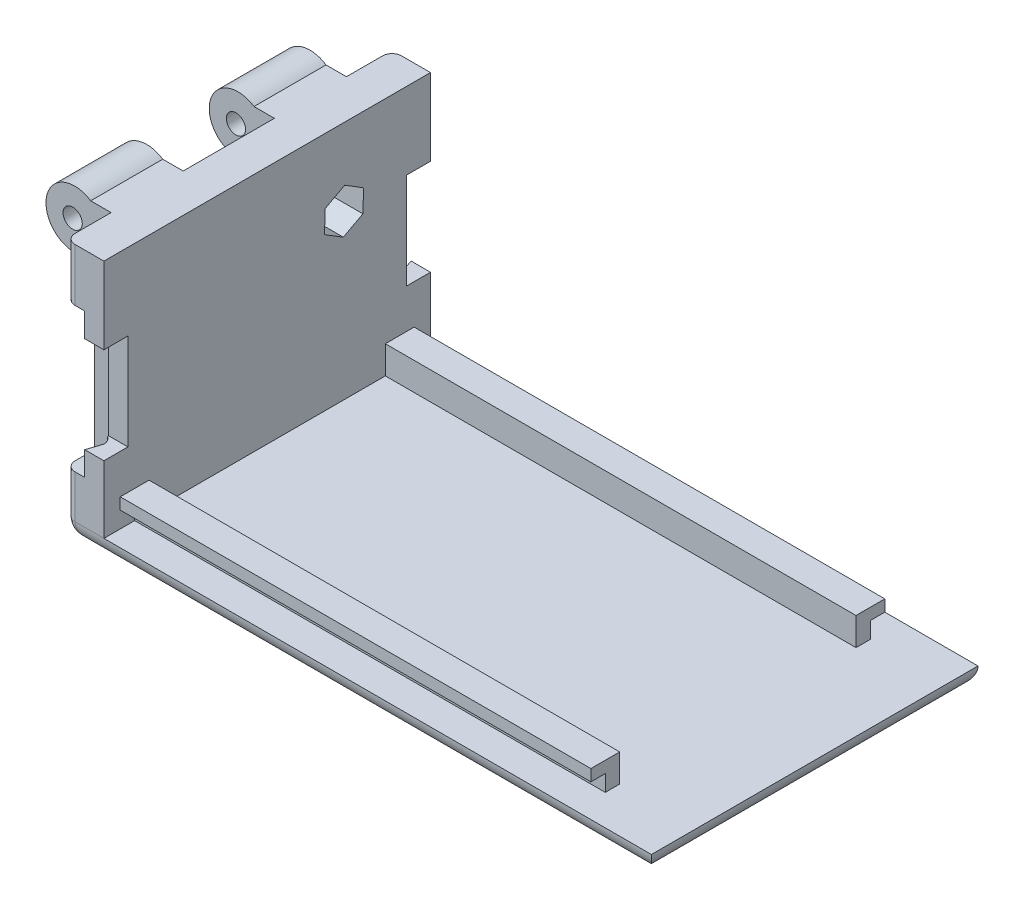
SolidWorks part; units mm, degrees
ref_plane "Front Plane" through (0, 0, 0) normal (0, 0, 1) x (1, 0, 0)
ref_plane "Top Plane" through (0, 0, 0) normal (0, 1, 0) x (1, 0, 0)
ref_plane "Right Plane" through (0, 0, 0) normal (1, 0, 0) x (0, 0, -1)
sketch "Sketch1" plane through (0, 0, 0) normal (0, 1, 0) x (1, 0, 0)
  line L1 (0, 0) -> (61, 0)
  line L2 (0, 0) -> (0, 34)
  line L3 (0, 34) -> (61, 34)
  line L4 (61, 0) -> (61, 34)
  line L5 (0, 0) -> (61, 34) construction
  line L6 (0, 34) -> (61, 0) construction
  point P4 (30.5, 17)
  dimension "D1" = 34
  dimension "D2" = 61
extrude "Boss-Extrude1" add sketch "Sketch1" along normal blind 2
sketch "Sketch2" plane through (0, 2, 0) normal (0, 1, 0) x (1, 0, 0)
  line L0 (61, 34) -> (0, 34) construction
  line L1 (0, 0) -> (4, 0)
  line L2 (0, 0) -> (0, 34)
  line L3 (0, 34) -> (4, 34)
  line L4 (4, 0) -> (4, 34)
  line L5 (0, 0) -> (4, 34) construction
  line L6 (0, 34) -> (4, 0) construction
  point P4 (2, 17)
  dimension "D1" = 4
extrude "Boss-Extrude2" add sketch "Sketch2" along normal blind 25 contours L4 L3 L2 L1
sketch "Sketch3" plane through (4, 0, 0) normal (1, 0, 0) x (0, 0, -1)
  line L0 (0, 2) -> (34, 2) construction
  line L1 (4.7, 2) -> (3.2, 2)
  line L2 (4.7, 2) -> (4.7, 4.9)
  line L3 (4.7, 4.9) -> (3.2, 4.9)
  line L4 (3.2, 2) -> (3.2, 4.9)
  line L5 (4.7, 2) -> (3.2, 4.9) construction
  line L6 (4.7, 4.9) -> (3.2, 2) construction
  line L7 (0, 27) -> (0, 2) construction
  line L8 (3.2, 4.9) -> (1.7, 4.9)
  line L9 (3.2, 4.9) -> (3.2, 3.7)
  line L10 (3.2, 3.7) -> (1.7, 3.7)
  line L11 (1.7, 4.9) -> (1.7, 3.7)
  line L12 (3.2, 4.9) -> (1.7, 3.7) construction
  line L13 (3.2, 3.7) -> (1.7, 4.9) construction
  line L14 (17, 2) -> (17, 9.9529) construction
  line L15 (30.8, 3.7) -> (32.3, 3.7)
  line L16 (32.3, 4.9) -> (32.3, 3.7)
  line L17 (30.8, 4.9) -> (32.3, 4.9)
  line L18 (30.8, 4.9) -> (30.8, 3.7)
  line L19 (29.3, 4.9) -> (30.8, 4.9)
  line L20 (30.8, 2) -> (30.8, 4.9)
  line L21 (29.3, 2) -> (30.8, 2)
  line L22 (29.3, 2) -> (29.3, 4.9)
  point P4 (3.95, 3.45)
  point P10 (2.45, 4.3)
  dimension "D1" = 1.2
  dimension "D2" = 2.9
  dimension "D3" = 1.5
  dimension "D4" = 3.2
  dimension "D5" = 1.5
extrude "Boss-Extrude3" add sketch "Sketch3" along normal blind 49 contours L17 L18 L15 L16 | L4 L1 L2 L3 | L8 L11 L10 L9 | L20 L21 L22 L19 region at (4, 4.3, -31.55)
sketch "Sketch4" plane through (0, 0, 0) normal (0, 0, 1) x (1, 0, 0)
  line L0 (0, 27) -> (0, 0) construction
  line L1 (4, 27) -> (0, 27)
  line L2 (4, 27) -> (4, 22)
  line L3 (4, 22) -> (0, 22)
  line L5 (4, 27) -> (-5, 22) construction
  line L6 (4, 22) -> (-3.9994, 26.8988) construction
  line L8 (0, 22) -> (-2.1254, 22)
  line L9 (0, 27) -> (-2.1254, 27)
  line L10 (0, 22) -> (0, 27)
  circle A1 centre (-3.7837, 24.5) radius 3
  point P4 (-0.281, 24.6217)
  line M12 (0, 27) -> (0, 0)
  dimension "D3" = 6
  dimension "D1" = 8
  dimension "D2" = 5
extrude "Boss-Extrude4" add sketch "Sketch4" against normal blind 30 contours M12 | A1 region at (-0.6518, 24.5, 0)
sketch "Sketch5" plane through (0, 0, 0) normal (0, -1, 0) x (1, 0, 0)
  line L0 (0, -34) -> (0, 0) construction
  line L1 (0, 0) -> (-8, 0)
  line L2 (0, 0) -> (0, -4.75)
  line L3 (0, -4.75) -> (-8, -4.75)
  line L4 (-8, 0) -> (-8, -4.75)
  line L5 (0, 0) -> (-8, -4.75) construction
  line L6 (0, -4.75) -> (-8, 0) construction
  line L7 (61, -34) -> (0, -34) construction
  line L8 (0, -29.25) -> (-8, -29.25)
  line L9 (0, -29.25) -> (0, -34)
  line L10 (0, -34) -> (-8, -34)
  line L11 (-8, -29.25) -> (-8, -34)
  line L12 (0, -29.25) -> (-8, -34) construction
  line L13 (0, -34) -> (-8, -29.25) construction
  line L14 (0, 0) -> (61, 0) construction
  line L16 (0, -12.25) -> (-8, -12.25)
  line L17 (0, -12.25) -> (0, -21.75)
  line L18 (0, -21.75) -> (-8, -21.75)
  line L19 (-8, -12.25) -> (-8, -21.75)
  line L20 (0, -12.25) -> (-8, -21.75) construction
  line L21 (0, -21.75) -> (-8, -12.25) construction
  point P4 (-4, -2.375)
  point P11 (-4, -31.625)
  point P20 (-4, -17)
  line M5 (0, 0) -> (0, -34)
  dimension "D1" = 4.75
  dimension "D2" = 4.75
  dimension "D3" = 0
  dimension "D4" = 0
  dimension "D5" = 8
  dimension "D6" = 8
  dimension "D7" = 12.25
  dimension "D8" = 12.25
extrude "Cut-Extrude1" cut sketch "Sketch5" against normal blind 30 contours L16 L19 L18 M5 | L3 L4 L1 L2 | L8 L11 L10 L9 region at (-4, 0, -17)
sketch "Sketch6" plane through (0, 0, 0) normal (0, 0, 1) x (1, 0, 0)
  line L1 (0, 27) -> (0, 0) construction
  circle A0 centre (-4, 24.5) radius 1
  dimension "D1" = 2
  dimension "D2" = 4
extrude "Cut-Extrude2" cut sketch "Sketch6" against normal through all
sketch "Sketch7" plane through (0, 0, 0) normal (-1, 0, 0) x (0, 0, 1)
  line L0 (0, 27) -> (0, 0) construction
  line L1 (-27.0352, 20.0914) -> (-26.9628, 17.7832)
  line L2 (-26.9628, 17.7832) -> (-24.9276, 16.6917)
  line L3 (-24.9276, 16.6917) -> (-22.9648, 17.9086)
  line L4 (-22.9648, 17.9086) -> (-23.0372, 20.2168)
  line L5 (-23.0372, 20.2168) -> (-25.0724, 21.3083)
  line L6 (-25.0724, 21.3083) -> (-27.0352, 20.0914)
  line L7 (0, 27) -> (-4.75, 27) construction
  circle A0 centre (-25, 19) radius 2 construction
  dimension "D1" = 4
  dimension "D2" = 25
  dimension "D3" = 8
extrude "Cut-Extrude3" cut sketch "Sketch7" against normal blind 28
fillet "Fillet1" radius 2 4 edges at (30.5, 0, 0) (61, 0, -17) (30.5, 0, -34) (0, 0, -17)
fillet "Fillet3" radius 1 4 edges at (0.5858, 0.5858, -33.4142) (0.5858, 0.5858, -0.5858) (0, 14.5, -34) (0, 14.5, 0)
sketch "Sketch8" plane through (0, 0, -34) normal (0, 0, -1) x (-1, 0, 0)
  line L0 (-1, 27) -> (-4, 27) construction
  line L1 (0, 6.5) -> (-2, 6.5)
  line L2 (0, 6.5) -> (0, 21.5)
  line L3 (0, 21.5) -> (-2, 21.5)
  line L4 (-2, 6.5) -> (-2, 21.5)
  line L5 (0, 6.5) -> (-2, 21.5) construction
  line L6 (0, 21.5) -> (-2, 6.5) construction
  line L7 (-4, 27) -> (-4, 2) construction
  point P4 (-1, 14)
  dimension "D1" = 5.5
  dimension "D2" = 15
  dimension "D3" = 2
  dimension "D4" = 2
extrude "Cut-Extrude4" cut sketch "Sketch8" against normal blind 3 contours L2 L3 L4 L1
sketch "Sketch9" plane through (2, 0, 0) normal (-1, 0, 0) x (0, 0, 1)
  line L0 (-34, 6.5) -> (-34, 21.5) construction
  line L1 (-34, 9) -> (-31.5, 9)
  line L2 (-34, 9) -> (-34, 19)
  line L3 (-34, 19) -> (-31.5, 19)
  line L4 (-31.5, 9) -> (-31.5, 19)
  line L5 (-34, 9) -> (-31.5, 19) construction
  line L6 (-34, 19) -> (-31.5, 9) construction
  line L7 (-31, 21.5) -> (-34, 21.5) construction
  point P4 (-32.75, 14)
  dimension "D1" = 10
  dimension "D2" = 2.5
  dimension "D3" = 2.5
extrude "Cut-Extrude5" cut sketch "Sketch9" against normal blind 3 contours L1 L4 L3 L2
sketch "Sketch11" plane through (0, 0, 0) normal (0, 0, 1) x (1, 0, 0)
  line L0 (1, 27) -> (4, 27) construction
  line L1 (2, 21.5) -> (0, 21.5)
  line L2 (2, 21.5) -> (2, 6.5)
  line L3 (2, 6.5) -> (0, 6.5)
  line L4 (0, 21.5) -> (0, 6.5)
  line L5 (2, 21.5) -> (0, 6.5) construction
  line L6 (2, 6.5) -> (0, 21.5) construction
  line L7 (4, 27) -> (4, 2) construction
  point P4 (1, 14)
  dimension "D1" = 15
  dimension "D2" = 5.5
  dimension "D3" = 2
extrude "Cut-Extrude6" cut sketch "Sketch11" against normal blind 3
sketch "Sketch12" plane through (2, 0, 0) normal (-1, 0, 0) x (0, 0, 1)
  line L0 (0, 6.5) -> (0, 21.5) construction
  line L1 (0, 9) -> (-2.5, 9)
  line L2 (0, 9) -> (0, 19)
  line L3 (0, 19) -> (-2.5, 19)
  line L4 (-2.5, 9) -> (-2.5, 19)
  line L5 (0, 9) -> (-2.5, 19) construction
  line L6 (0, 19) -> (-2.5, 9) construction
  line L7 (0, 6.5) -> (-1, 6.5) construction
  point P4 (-1.25, 14)
  dimension "D1" = 10
  dimension "D2" = 2.5
  dimension "D3" = 2.5
extrude "Cut-Extrude7" cut sketch "Sketch12" against normal blind 3
sketch "Sketch13" plane through (0, 0, 0) normal (0, -1, 0) x (-1, 0, 0)
  line L0 (-2, 12) -> (-59, 12) construction
  line L1 (-2, 2) -> (-2, 32) construction
  line L2 (-59, 32) -> (-59, 2) construction
  line L3 (-59, 2) -> (-2, 2) construction
  text T0 "FLEXI" font "Century Gothic" height in points 45
  dimension "D1" = 10
extrude "Cut-Extrude8" cut sketch "Sketch13" against normal blind 1.2
sketch "Sketch14" plane through (0, 6.5, 0) normal (0, 1, 0) x (1, 0, 0)
  line L0 (2, 31) -> (2, 34) construction
  line L1 (2, 34) -> (2, 33.1301)
  line L2 (2, 34) -> (2.5, 32.2641)
  arc A0 (2, 33.1301) -> (2.5, 32.2641) centre (1.5, 32.2641) ccw
  dimension "D1" = 2
  dimension "D2" = 0.5
extrude "Cut-Extrude9" cut sketch "Sketch14" along normal blind 15
sketch "Sketch15" plane through (0, 21.5, 0) normal (0, -1, 0) x (1, 0, 0)
  line L0 (2, 0) -> (1, 0) construction
  line L1 (2, -3) -> (2, 0) construction
  line L2 (2, 0) -> (2.5, -1.5)
  line L3 (2, 0) -> (2, -0.634)
  arc A0 (2, -0.634) -> (2.5, -1.5) centre (1.5, -1.5) ccw
  dimension "D1" = 2
  dimension "D2" = 1.5
  dimension "D3" = 0.5
extrude "Cut-Extrude10" cut sketch "Sketch15" along normal blind 15
